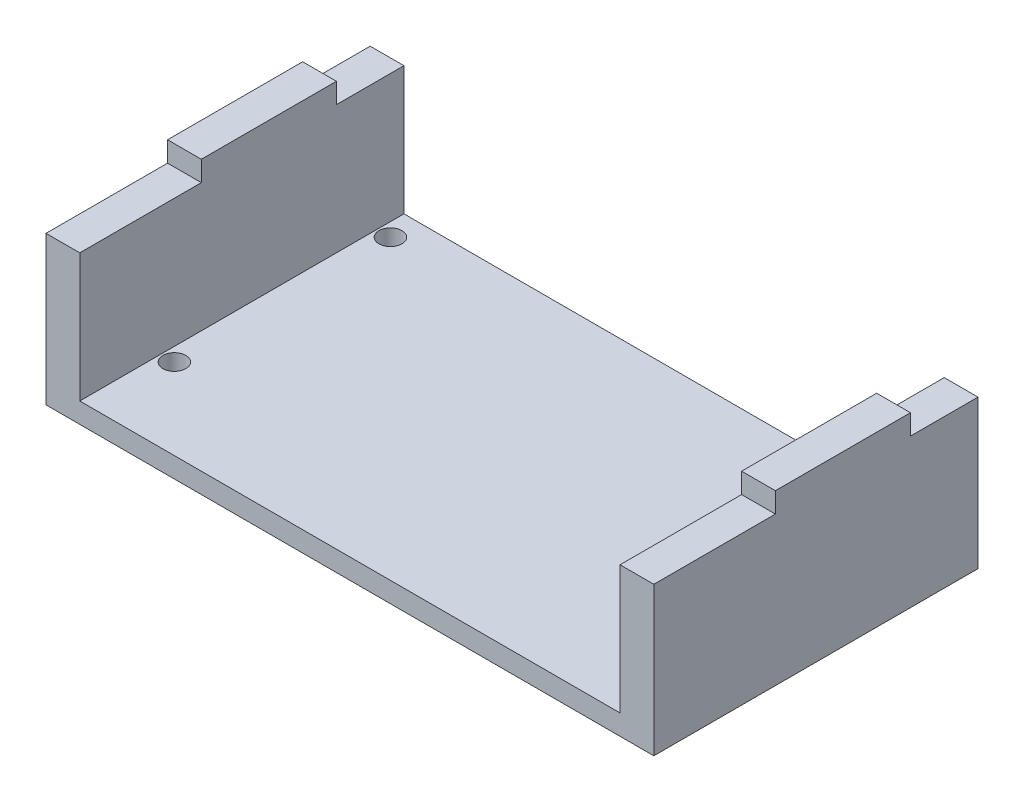
SolidWorks part; units mm, degrees
ref_plane "Front Plane" through (0, 0, 0) normal (0, 0, 1) x (1, 0, 0)
ref_plane "Top Plane" through (0, 0, 0) normal (0, 1, 0) x (1, 0, 0)
ref_plane "Right Plane" through (0, 0, 0) normal (1, 0, 0) x (0, 0, -1)
sketch "Sketch1" plane through (0, 0, 0) normal (0, 1, 0) x (1, 0, 0)
  line L1 (-45, 20) -> (45, 20)
  line L2 (-45, 20) -> (-45, -28)
  line L3 (-45, -28) -> (45, -28)
  line L4 (45, 20) -> (45, -28)
  point P4 (0, 0)
  point P5 (0, 0)
  point P6 (0, 0)
  point P7 (0, 0)
  point P8 (0, 0)
  point P9 (0, 0)
  point P10 (0, 0)
extrude "Boss-Extrude1" add sketch "Sketch1" along normal blind 3
sketch "Sketch2" plane through (0, 3, 0) normal (0, 1, 0) x (1, 0, 0)
  line L1 (-45, 20) -> (-40, 20)
  line L2 (-45, 20) -> (-45, -28)
  line L3 (-45, -28) -> (-40, -28)
  line L4 (-40, 20) -> (-40, -28)
  point P4 (0, 0)
  point P5 (0, 0)
  point P6 (0, 0)
extrude "Boss-Extrude2" add sketch "Sketch2" along normal blind 22
sketch "Sketch3" plane through (0, 3, 0) normal (0, 1, 0) x (1, 0, 0)
  line L1 (40, 20) -> (45, 20)
  line L2 (40, 20) -> (40, -28)
  line L3 (40, -28) -> (45, -28)
  line L4 (45, 20) -> (45, -28)
  point P4 (0, 0)
extrude "Boss-Extrude3" add sketch "Sketch3" along normal blind 22
sketch "Sketch4" plane through (0, 25, 0) normal (0, 1, 0) x (1, 0, 0)
  line L0 (-45, 20) -> (-45, -28) construction
  line L1 (-45, 20) -> (-40, 20)
  line L2 (-45, 20) -> (-45, 10)
  line L3 (-45, 10) -> (-40, 10)
  line L4 (-40, 20) -> (-40, 10)
  line L6 (-45, -10) -> (-40, -10)
  line L7 (-45, -10) -> (-45, -28)
  line L8 (-45, -28) -> (-40, -28)
  line L9 (-40, -10) -> (-40, -28)
  line L10 (40, 20) -> (45, 20)
  line L11 (40, 20) -> (40, 10)
  line L12 (40, 10) -> (45, 10)
  line L13 (45, 20) -> (45, 10)
  line L14 (40, -10) -> (45, -10)
  line L15 (40, -10) -> (40, -28)
  line L16 (40, -28) -> (45, -28)
  line L17 (45, -10) -> (45, -28)
  point P18 (0, 0)
  point P19 (0, 0)
  point P20 (0, 0)
  point P21 (0, 0)
  point P22 (0, 0)
  point P23 (0, 0)
extrude "Cut-Extrude1" cut sketch "Sketch4" against normal blind 3
hole_wizard "M3 Clearance Hole1" positions "Sketch5" profile "Sketch6" hole size "M3" standard "ANSI Metric"
sketch "Sketch5" plane through (0, 0, 0) normal (0, -1, 0) x (-1, 0, 0)
  point P0 (-38, 16)
  point P2 (-38, -16)
  point P4 (38, -16)
  point P6 (38, 16)
  point P9 (0, 0)
  point P10 (0, 0)
  point P11 (0, 0)
  point P12 (0, 0)
sketch "Sketch6" plane through (38, 0, -16) normal (1, 0, 0) x (0, 0, -1)
  line L0 (0, 0) -> (0, 6.0215)
  line L1 (0, 6.0215) -> (1.7, 5)
  line L2 (1.7, 5) -> (1.7, 0)
  line L5 (1.7, 0) -> (0, 0)
  line L10 (0, 6.0215) -> (-1.7, 5) construction
  line L11 (0, -6.35) -> (0, 107.95) construction
  dimension "Hole Dia." = 3.4
  dimension "Hole Depth" = 5
  dimension "Drill Angle" = 118
ref_plane "Plane14" through (-40, 22, -20) normal (-1, 0, 0) x (0, 0, 1)
